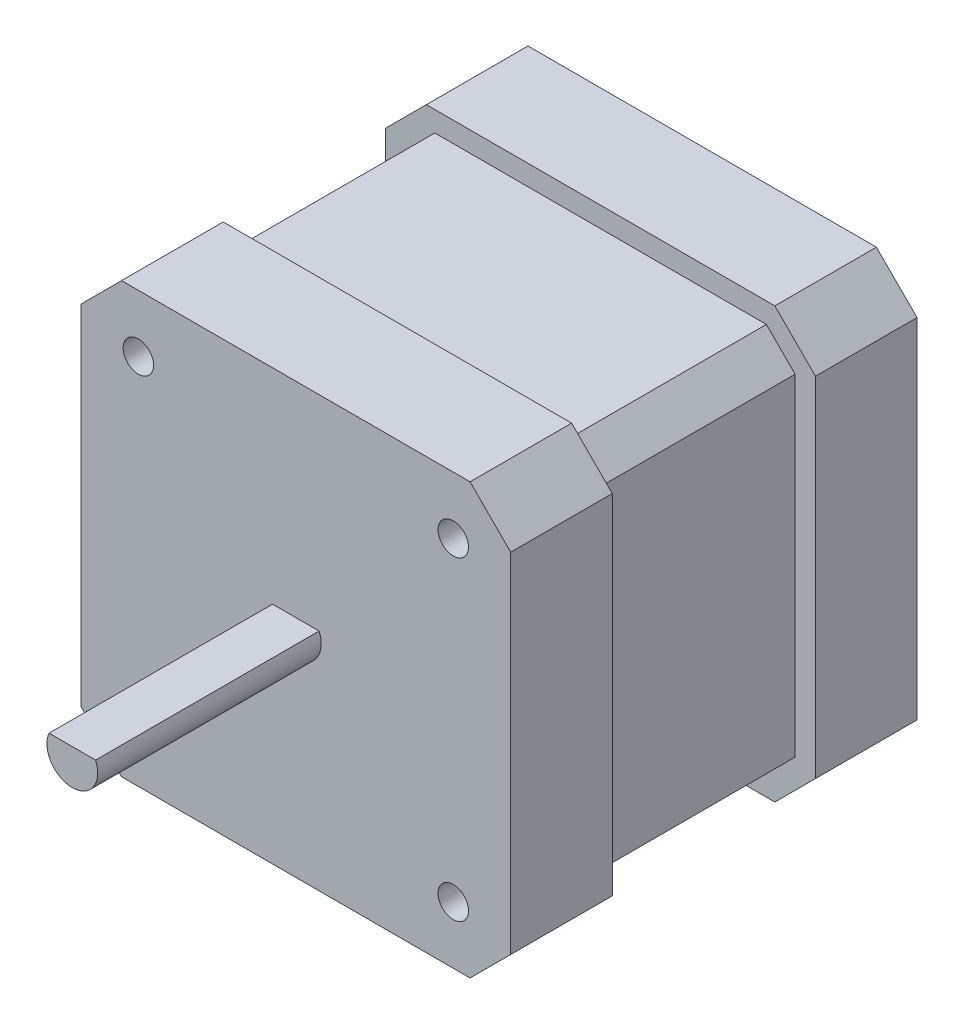
SolidWorks part; units mm, degrees
ref_plane "Front Plane" through (0, 0, 0) normal (0, 0, 1) x (1, 0, 0)
ref_plane "Top Plane" through (0, 0, 0) normal (0, 1, 0) x (1, 0, 0)
ref_plane "Right Plane" through (0, 0, 0) normal (1, 0, 0) x (0, 0, -1)
sketch "Sketch1" plane through (0, 0, 0) normal (0, 0, 1) x (1, 0, 0)
  line L0 (-21.15, 17.15) -> (-17.15, 21.15)
  line L1 (-17.15, -21.15) -> (17.15, -21.15)
  line L2 (-21.15, -17.15) -> (-21.15, 17.15)
  line L3 (-17.15, 21.15) -> (17.15, 21.15)
  line L4 (21.15, -17.15) -> (21.15, 17.15)
  line L5 (-21.15, -21.15) -> (21.15, 21.15) construction
  line L6 (-21.15, 21.15) -> (21.15, -21.15) construction
  line L7 (17.15, 21.15) -> (21.15, 17.15)
  line L8 (17.15, -21.15) -> (21.15, -17.15)
  line L9 (-21.15, -17.15) -> (-17.15, -21.15)
  point P0 (0, 0)
  dimension "D1" = 42.3
  dimension "D2" = 42.3
extrude "Boss-Extrude1" add sketch "Sketch1" along normal blind 10 contours L3 L7 L4 L8 L1 L9 L2 L0
sketch "Sketch2" plane through (0, 0, 0) normal (0, 0, -1) x (-1, 0, 0)
  line L16 (19.15, 16.3216) -> (16.3216, 19.15)
  line L17 (16.3216, 19.15) -> (-16.3216, 19.15)
  line L18 (-16.3216, 19.15) -> (-19.15, 16.3216)
  line L19 (-19.15, 16.3216) -> (-19.15, -16.3216)
  line L20 (-19.15, -16.3216) -> (-16.3216, -19.15)
  line L21 (-16.3216, -19.15) -> (16.3216, -19.15)
  line L22 (16.3216, -19.15) -> (19.15, -16.3216)
  line L23 (19.15, -16.3216) -> (19.15, 16.3216)
  line L24 (19.15, 16.3216) -> (16.3216, 19.15)
  line L25 (16.3216, 19.15) -> (-16.3216, 19.15)
  line L26 (-16.3216, 19.15) -> (-19.15, 16.3216)
  line L27 (-19.15, 16.3216) -> (-19.15, -16.3216)
  line L28 (-19.15, -16.3216) -> (-16.3216, -19.15)
  line L29 (-16.3216, -19.15) -> (16.3216, -19.15)
  line L30 (16.3216, -19.15) -> (19.15, -16.3216)
  line L31 (19.15, -16.3216) -> (19.15, 16.3216)
  dimension "D1" = 2
extrude "Boss-Extrude2" add sketch "Sketch2" along normal blind 20
sketch "Sketch3" plane through (0, 0, -20) normal (0, 0, -1) x (-1, 0, 0)
  line L8 (21.15, 17.15) -> (17.15, 21.15)
  line L9 (17.15, 21.15) -> (-17.15, 21.15)
  line L10 (-17.15, 21.15) -> (-21.15, 17.15)
  line L11 (-21.15, 17.15) -> (-21.15, -17.15)
  line L12 (-21.15, -17.15) -> (-17.15, -21.15)
  line L13 (-17.15, -21.15) -> (17.15, -21.15)
  line L14 (17.15, -21.15) -> (21.15, -17.15)
  line L15 (21.15, -17.15) -> (21.15, 17.15)
  line L16 (21.15, 17.15) -> (17.15, 21.15)
  line L17 (17.15, 21.15) -> (-17.15, 21.15)
  line L18 (-17.15, 21.15) -> (-21.15, 17.15)
  line L19 (-21.15, 17.15) -> (-21.15, -17.15)
  line L20 (-21.15, -17.15) -> (-17.15, -21.15)
  line L21 (-17.15, -21.15) -> (17.15, -21.15)
  line L22 (17.15, -21.15) -> (21.15, -17.15)
  line L23 (21.15, -17.15) -> (21.15, 17.15)
  dimension "D1" = 0
extrude "Boss-Extrude3" add sketch "Sketch3" along normal blind 10
sketch "Sketch4" plane through (0, 0, 10) normal (0, 0, 1) x (1, 0, 0)
  line L0 (-2.2913, 1) -> (2.2913, 1)
  circle A0 centre (0, 0) radius 2.5
  dimension "D1" = 5
  dimension "D2" = 1
extrude "Boss-Extrude4" add sketch "Sketch4" along normal blind 22 contours L0 A0 region at (0, -0.5463, 10)
sketch "Sketch6" plane through (0, 0, 10) normal (0, 0, 1) x (1, 0, 0)
  line L1 (-15.5, -15.5) -> (15.5, -15.5) construction
  line L2 (-15.5, -15.5) -> (-15.5, 15.5) construction
  line L3 (-15.5, 15.5) -> (15.5, 15.5) construction
  line L4 (15.5, -15.5) -> (15.5, 15.5) construction
  line L5 (-15.5, -15.5) -> (15.5, 15.5) construction
  line L6 (-15.5, 15.5) -> (15.5, -15.5) construction
  circle A0 centre (-15.5, 15.5) radius 1.5
  circle A1 centre (15.5, 15.5) radius 1.5
  circle A2 centre (15.5, -15.5) radius 1.5
  circle A3 centre (-15.5, -15.5) radius 1.5
  point P0 (0, 0)
  dimension "D3" = 3
  dimension "D1" = 31
  dimension "D2" = 31
extrude "Cut-Extrude1" cut sketch "Sketch6" against normal blind 4.5
